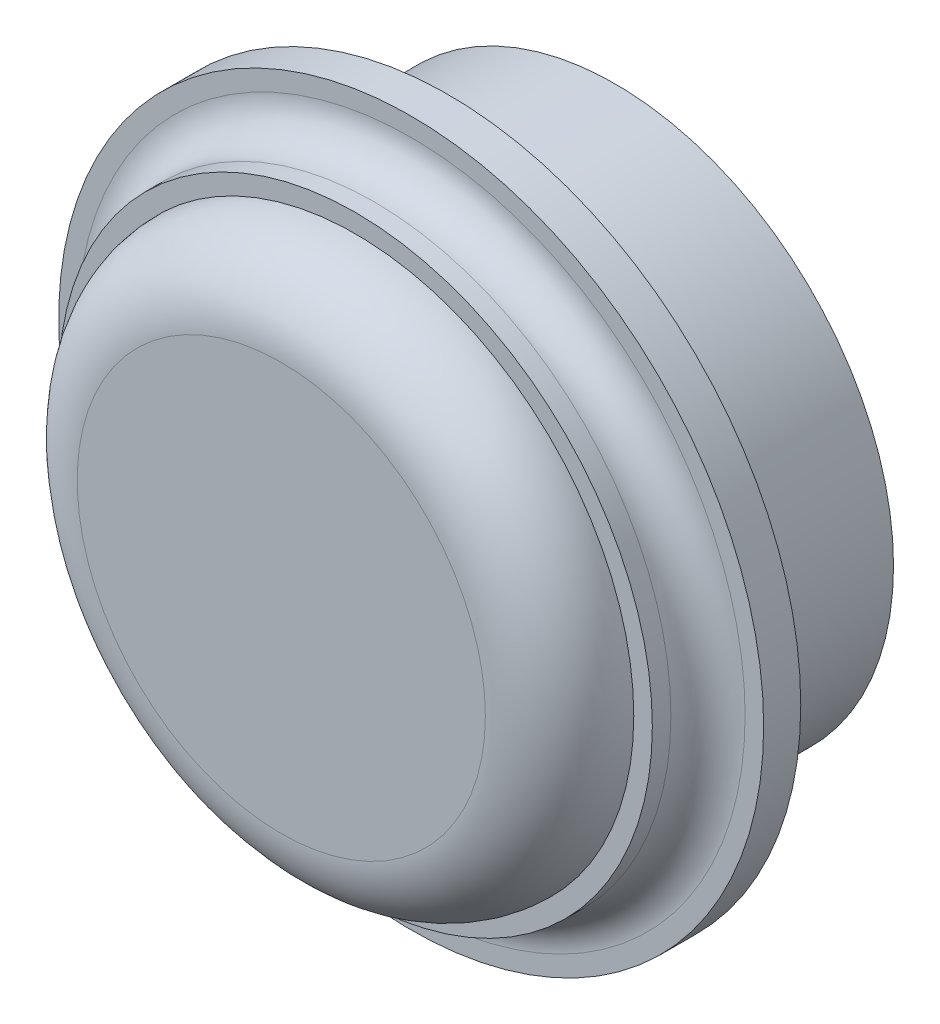
SolidWorks part; units mm, degrees
note: The reader was unsure of these and kept them because the rebuilt part matched: shared geometry of "Sketch4<2>".
ref_plane "Front Plane" through (0, 0, 0) normal (0, 0, 1) x (1, 0, 0)
ref_plane "Top Plane" through (0, 0, 0) normal (0, 1, 0) x (1, 0, 0)
ref_plane "Right Plane" through (0, 0, 0) normal (1, 0, 0) x (0, 0, -1)
sketch "Sketch1" plane through (0, 0, 0) normal (0, 0, 1) x (1, 0, 0)
  circle A0 centre (0, 0) radius 95
  circle A1 centre (0, 0) radius 75
  dimension "D1" = 150
  dimension "D2" = 190
extrude "Boss-Extrude1" add sketch "Sketch1" along normal blind 10
sketch "Sketch2" plane through (0, 0, 10) normal (0, 0, 1) x (1, 0, 0)
  circle A0 centre (0, 0) radius 75
surface "Surface-Extrude1" sketch "Sketch2" parameters "D1"=15
thicken "Thicken1" surfaces to thicken 102 thickness 5 parameters "D1"=5
sketch "Sketch4" plane through (0, 0, 0) normal (0, 0, 1) x (1, 0, 0)
  circle A0 centre (0, 0) radius 75
extrude "Boss-Extrude2" add sketch "Sketch4" along normal blind 45 separate body
fillet "Fillet1" radius 20 1 edges at (75, 0, 45)
extrude "Boss-Extrude3" add sketch "Sketch4<2>" against normal blind 45 separate body
sketch "Sketch4<2>" plane through (0, 0, 0) normal (0, 0, 1) x (1, 0, 0) same geometry as "Sketch4"
fillet "Fillet2" radius 10 1 edges at (80, 0, 10)
